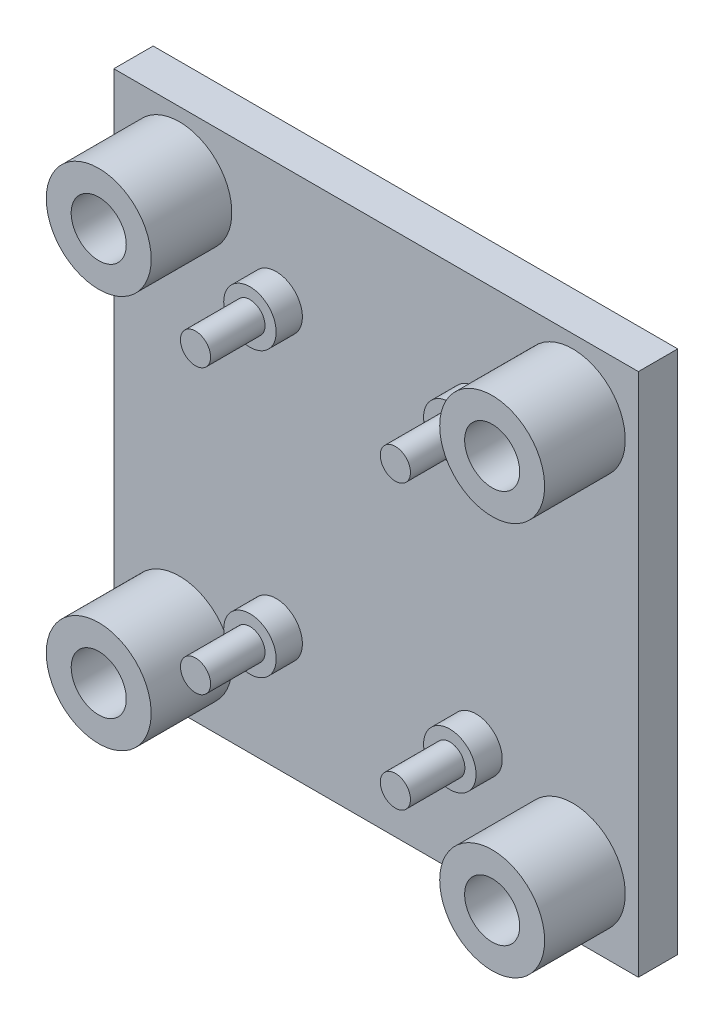
SolidWorks part; units mm, degrees
material "ABS"
ref_plane "前基準面" through (0, 0, 0) normal (0, 0, 1) x (1, 0, 0)
ref_plane "上基準面" through (0, 0, 0) normal (0, 1, 0) x (1, 0, 0)
ref_plane "右基準面" through (0, 0, 0) normal (1, 0, 0) x (0, 0, -1)
sketch "草圖1" plane through (0, 0, 0) normal (0, 0, 1) x (1, 0, 0)
  line L1 (-20, -20) -> (20, -20)
  line L2 (-20, -20) -> (-20, 20)
  line L3 (-20, 20) -> (20, 20)
  line L4 (20, -20) -> (20, 20)
  line L5 (-20, -20) -> (20, 20) construction
  line L6 (-20, 20) -> (20, -20) construction
  point P0 (0, 0)
  dimension "D1" = 40
  dimension "D2" = 40
extrude "填料-伸長1" add sketch "草圖1" along normal blind 3
sketch "草圖2" plane through (0, 0, 3) normal (0, 0, 1) x (1, 0, 0)
  line L0 (0, 20) -> (0, -20) construction
  line L1 (20, 20) -> (-20, 20) construction
  line L2 (-20, -20) -> (20, -20) construction
  line L3 (-20, 0) -> (20, 0) construction
  line L4 (-20, 20) -> (-20, -20) construction
  line L5 (20, -20) -> (20, 20) construction
  circle A0 centre (-7.62, 10.795) radius 2
  circle A1 centre (-7.62, -10.795) radius 2
  circle A2 centre (7.62, 10.795) radius 2
  circle A3 centre (7.62, -10.795) radius 2
  dimension "D1" = 4
  dimension "D2" = 7.62
  dimension "D3" = 10.795
extrude "填料-伸長2" add sketch "草圖2" along normal blind 2
sketch "草圖3" plane through (0, 0, 5) normal (0, 0, 1) x (1, 0, 0)
  line L0 (0, 20) -> (0, -20) construction
  line L1 (20, 0) -> (-20, 0) construction
  line L2 (20, -20) -> (20, 20) construction
  line L3 (-20, 20) -> (-20, -20) construction
  line L4 (20, 20) -> (-20, 20) construction
  line L5 (-20, -20) -> (20, -20) construction
  circle A0 centre (-7.62, 10.795) radius 1.15
  circle A1 centre (-7.62, -10.795) radius 1.15
  circle A2 centre (7.62, -10.795) radius 1.15
  circle A3 centre (7.62, 10.795) radius 1.15
  dimension "D1" = 2.3
extrude "填料-伸長3" add sketch "草圖3" along normal blind 4.15
sketch "草圖4" plane through (0, 0, 3) normal (0, 0, 1) x (1, 0, 0)
  line L0 (-20, 0) -> (20, 0) construction
  line L1 (-20, 20) -> (-20, -20) construction
  line L2 (20, -20) -> (20, 20) construction
  line L3 (0, 20) -> (0, -20) construction
  line L4 (20, 20) -> (-20, 20) construction
  line L5 (-20, -20) -> (20, -20) construction
  circle A0 centre (-15, 15) radius 4
  circle A1 centre (-15, -15) radius 4
  circle A2 centre (15, -15) radius 4
  circle A3 centre (15, 15) radius 4
  dimension "D1" = 15
  dimension "D2" = 15
  dimension "D3" = 8
extrude "填料-伸長4" add sketch "草圖4" along normal blind 6.15
sketch "草圖5" plane through (0, 0, 9.15) normal (0, 0, 1) x (1, 0, 0)
  line L0 (-20, 0) -> (20, 0) construction
  line L1 (0, 20) -> (0, -20) construction
  line L2 (-20, 20) -> (-20, -20) construction
  line L3 (20, 20) -> (-20, 20) construction
  line L4 (20, -20) -> (20, 20) construction
  line L5 (-20, -20) -> (20, -20) construction
  circle A0 centre (-15, 15) radius 2.1
  circle A1 centre (-15, -15) radius 2.1
  circle A2 centre (15, -15) radius 2.1
  circle A3 centre (15, 15) radius 2.1
  dimension "D1" = 4.2
extrude "除料-伸長1" cut sketch "草圖5" against normal through all
